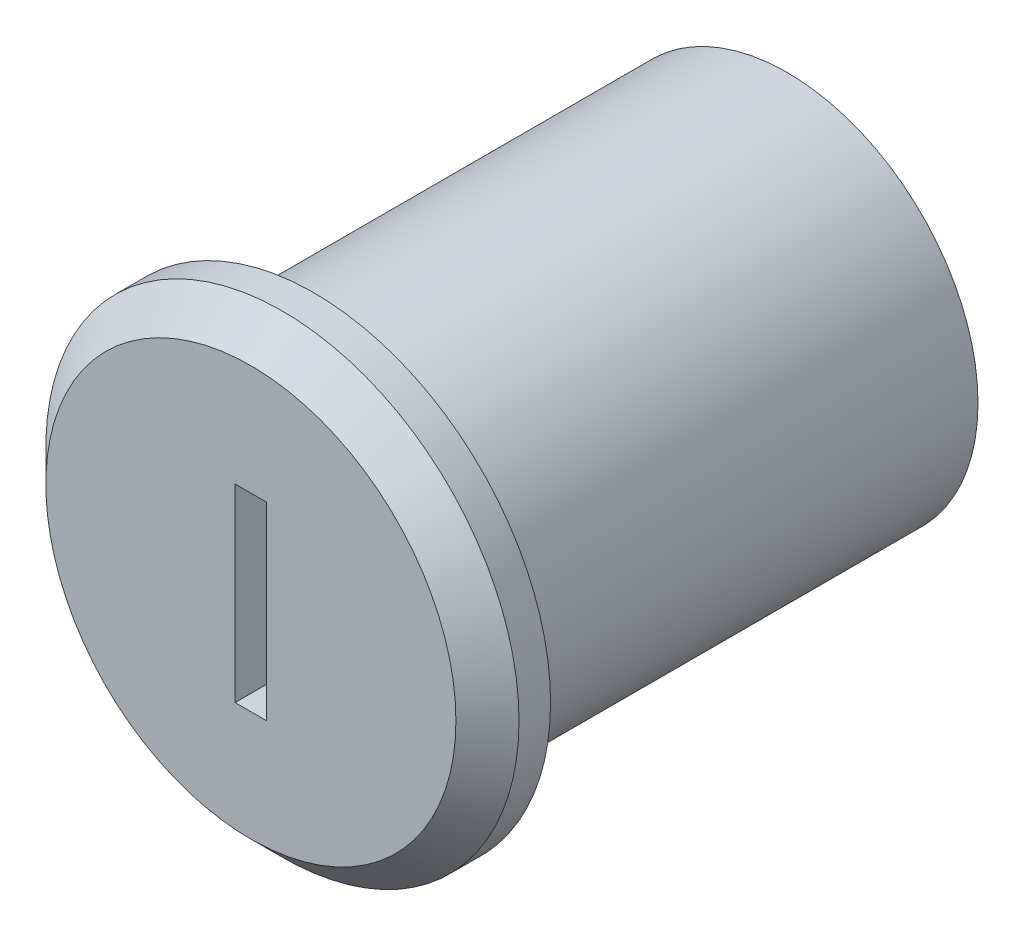
SolidWorks part; units mm, degrees
ref_plane "Front" through (0, 0, 0) normal (0, 0, 1) x (1, 0, 0)
ref_plane "Top" through (0, 0, 0) normal (0, 1, 0) x (1, 0, 0)
ref_plane "Right" through (0, 0, 0) normal (1, 0, 0) x (0, 0, -1)
sketch "Sketch1" plane through (0, 0, 0) normal (0, 0, 1) x (1, 0, 0)
  circle A0 centre (0, 0) radius 6.05
  dimension "D1" = 12.1
extrude "Boss-Extrude1" add sketch "Sketch1" against normal blind 15
sketch "Sketch2" plane through (0, 0, 0) normal (0, 0, 1) x (1, 0, 0)
  circle A0 centre (0, 0) radius 7.5
  dimension "D1" = 15
extrude "Boss-Extrude2" add sketch "Sketch2" along normal blind 1
sketch "Sketch3" plane through (0, 0, 1) normal (0, 0, 1) x (1, 0, 0)
  circle A1 centre (0, 0) radius 7.5
  circle A2 centre (0, 0) radius 7.5
  dimension "D1" = 0
extrude "Boss-Extrude3" add sketch "Sketch3" along normal blind 1 draft 45
sketch "Sketch4" plane through (0, 0, 2) normal (0, 0, 1) x (1, 0, 0)
  line L1 (-0.5, -3) -> (0.5, -3)
  line L2 (-0.5, -3) -> (-0.5, 3)
  line L3 (-0.5, 3) -> (0.5, 3)
  line L4 (0.5, -3) -> (0.5, 3)
  line L5 (-0.5, -3) -> (0.5, 3) construction
  line L6 (-0.5, 3) -> (0.5, -3) construction
  point P0 (0, 0)
  dimension "D1" = 1
  dimension "D2" = 6
extrude "Cut-Extrude1" cut sketch "Sketch4" against normal blind 1
sketch "Panel Cut Guide" plane through (0, 0, 0) normal (0, 0, 1) x (1, 0, 0)
  circle A0 centre (0, 0) radius 6.075
  dimension "D1" = 12.15
